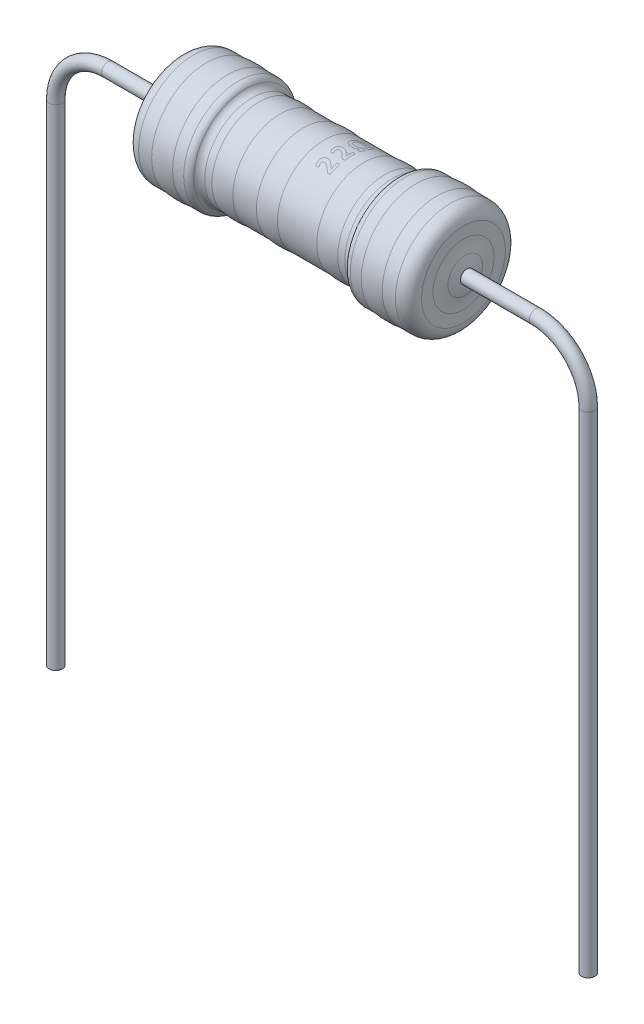
SolidWorks part; units mm, degrees
ref_plane "Front Plane" through (0, 0, 0) normal (0, 0, 1) x (1, 0, 0)
ref_plane "Top Plane" through (0, 0, 0) normal (0, 1, 0) x (1, 0, 0)
ref_plane "Right Plane" through (0, 0, 0) normal (1, 0, 0) x (0, 0, -1)
sketch "Sketch Set Wire Width" plane through (0, 0, 0) normal (0, 0, 1) x (1, 0, 0)
  line L0 (-8.16, 0) -> (8.16, 0)
  line L1 (-10.16, -2) -> (-10.16, -20.6984)
  line L2 (10.16, -2) -> (10.16, -20.6984)
  line L3 (-10.16, -20.6984) -> (10.16, -20.6984) construction
  line L4 (0, 0) -> (0, -20.6984) construction
  arc A0 (-8.16, 0) -> (-10.16, -2) centre (-8.16, -2) ccw
  arc A1 (8.16, 0) -> (10.16, -2) centre (8.16, -2) cw
  dimension "D2" = 2
  dimension "D3" = 60
  dimension "D1" = 20.32
sketch "Sketch Wire Diameter" plane through (0, 0, 0) normal (1, 0, 0) x (0, 0, -1)
  circle A0 centre (0, 0) radius 0.25
  dimension "D1" = 0.5
sweep "SET WIRE LENGTH" add profiles "Sketch Wire Diameter" path "Sketch Set Wire Width"
sketch "Sketch3" plane through (0, 0, 0) normal (0, 0, 1) x (1, 0, 0)
  line L0 (-5.4, 0) -> (5.4, 0)
  line L1 (0, 0) -> (0, 1.8) construction
  line L2 (-2.9, 1.8) -> (2.9, 1.8)
  line L3 (-5.4, 0) -> (-5.4, 1.6)
  line L4 (-4.9, 2.1) -> (-3.18, 2.1)
  line L5 (-2.9, 1.82) -> (-2.9, 1.8)
  line L6 (5.4, 0) -> (5.4, 1.6)
  line L7 (4.9, 2.1) -> (3.18, 2.1)
  line L8 (2.9, 1.82) -> (2.9, 1.8)
  arc A0 (-5.4, 1.6) -> (-4.9, 2.1) centre (-4.9, 1.6) cw
  arc A1 (5.4, 1.6) -> (4.9, 2.1) centre (4.9, 1.6) ccw
  arc A2 (-3.18, 2.1) -> (-2.9, 1.82) centre (-3.18, 1.82) cw
  arc A3 (3.18, 2.1) -> (2.9, 1.82) centre (3.18, 1.82) ccw
  dimension "D5" = 0.5
  dimension "D6" = 0.28
  dimension "D1" = 10.8
  dimension "D2" = 5.8
  dimension "D3" = 1.8
  dimension "D4" = 2.1
revolve "Revolve2" add sketch "Sketch3" angle 360 about L0
fillet "Fillet1" radius 0.3 2 edges at (2.9, 0, 1.8) (-2.9, 0, 1.8)
sketch "Sketch5" plane through (0, 0, 0) normal (0, 0, 1) x (1, 0, 0)
  line L0 (0, 0) -> (2, 0) construction
  line L1 (0, 0) -> (-0.3, 0) construction
  line L2 (-0.3, 0) -> (-2, 0) construction
  line L3 (-2, 0) -> (-4, 0) construction
  line L4 (2, 0) -> (4, 0) construction
  line L5 (-4, 0) -> (-4, 2.1) construction
  line L6 (-0.3, 0) -> (-0.3, 1.8) construction
  line L7 (-2, 0) -> (-2, 1.8) construction
  line L8 (2, 0) -> (2, 1.8) construction
  line L9 (4, 0) -> (4, 2.1) construction
  line L10 (-4, 2.1) -> (-4, 2.13) construction
  line L11 (-4.9, 2.1) -> (-3.18, 2.1) construction
  line L12 (4.9, 2.1) -> (3.18, 2.1) construction
  line L13 (-2.9, 1.8) -> (2.9, 1.8) construction
  line L14 (-2, 1.8) -> (-2, 1.83) construction
  line L17 (-4.4, 2.1) -> (-3.6, 2.1)
  line L19 (-5.4, 0) -> (5.4, 0) construction
  line L22 (-2.4, 1.8) -> (-1.6, 1.8) construction
  line L26 (-0.7, 1.8) -> (0.1, 1.8) construction
  line L30 (1.6, 1.8) -> (2.4, 1.8) construction
  line L34 (3.6, 2.1) -> (4.4, 2.1) construction
  line L36 (-0.3, 1.8) -> (-0.3, 1.83) construction
  line L37 (2, 1.8) -> (2, 1.83) construction
  line L38 (4, 2.1) -> (4, 2.13) construction
  arc A0 (-4.4, 2.1) -> (-3.6, 2.1) centre (-4, -0.5517) cw
  arc A1 (-2.4, 1.8) -> (-1.6, 1.8) centre (-2, -0.8517) cw construction
  arc A2 (-0.7, 1.8) -> (0.1, 1.8) centre (-0.3, -0.8517) cw construction
  arc A3 (1.6, 1.8) -> (2.4, 1.8) centre (2, -0.8517) cw construction
  arc A4 (3.6, 2.1) -> (4.4, 2.1) centre (4, -0.5517) cw construction
  dimension "D3" = 0.8
  dimension "D1" = 4
  dimension "D2" = 4
  dimension "D4" = 0.03
  dimension "D5" = 2
  dimension "D6" = 2
  dimension "D7" = 1.7
revolve "Band 1" add sketch "Sketch5" angle 360 about L2
sketch "Sketch8" plane through (0, 0, 0) normal (0, 0, 1) x (1, 0, 0)
  line L0 (-2.4, 1.8) -> (-1.6, 1.8) construction
  line L1 (-2.4, 1.8) -> (-1.6, 1.8)
  arc A0 (-1.6, 1.8) -> (-2.4, 1.8) centre (-2, -0.8517) ccw construction
  arc A1 (-1.6, 1.8) -> (-2.4, 1.8) centre (-2, -0.8517) ccw
revolve "Band 2" add sketch "Sketch8" angle 360 about L2
sketch "Sketch9" plane through (0, 0, 0) normal (0, 0, 1) x (1, 0, 0)
  line L0 (-0.7, 1.8) -> (0.1, 1.8) construction
  line L1 (-0.7, 1.8) -> (0.1, 1.8)
  arc A0 (0.1, 1.8) -> (-0.7, 1.8) centre (-0.3, -0.8517) ccw construction
  arc A1 (0.1, 1.8) -> (-0.7, 1.8) centre (-0.3, -0.8517) ccw
revolve "Band 3" add sketch "Sketch9" angle 360 about L2
sketch "Sketch10" plane through (0, 0, 0) normal (0, 0, 1) x (1, 0, 0)
  line L0 (1.6, 1.8) -> (2.4, 1.8) construction
  line L1 (1.6, 1.8) -> (2.4, 1.8)
  arc A0 (2.4, 1.8) -> (1.6, 1.8) centre (2, -0.8517) ccw construction
  arc A1 (2.4, 1.8) -> (1.6, 1.8) centre (2, -0.8517) ccw
revolve "Band 4" add sketch "Sketch10" angle 360 about L0
sketch "Sketch11" plane through (0, 0, 0) normal (0, 0, 1) x (1, 0, 0)
  line L0 (3.6, 2.1) -> (4.4, 2.1) construction
  line L1 (3.6, 2.1) -> (4.4, 2.1)
  arc A0 (4.4, 2.1) -> (3.6, 2.1) centre (4, -0.5517) ccw construction
  arc A1 (4.4, 2.1) -> (3.6, 2.1) centre (4, -0.5517) ccw
revolve "Band 5" add sketch "Sketch11" angle 360 about L4
sketch "Sketch12" plane through (0, 0, 0) normal (0, 0, 1) x (1, 0, 0)
  line L0 (-5.35, 0) -> (5.35, 0) construction
  line L1 (-5.35, 1) -> (-5.35, 0)
  line L2 (5.35, 1) -> (5.35, 0)
  line L3 (-5.35, 0) -> (-5.55, 0)
  line L4 (5.35, 0) -> (5.55, 0)
  arc A0 (-5.35, 1) -> (-5.55, 0) centre (-2.95, 0) ccw
  arc A1 (5.35, 1) -> (5.55, 0) centre (2.95, 0) cw
  dimension "D3" = 0.2
  dimension "D4" = 2.6
  dimension "D1" = 10.7
  dimension "D2" = 1
revolve "Revolve10" add sketch "Sketch12" angle 360 about L0
fillet "Fillet2" radius 2 2 edges at (5.4, 0, 0.8703) (-5.4, 0, -0.8703)
ref_plane "Plane2" through (0, 3, 0) normal (0, 1, 0) x (1, 0, 0)
sketch "Sketch13" plane through (0, 3, 0) normal (0, 1, 0) x (1, 0, 0)
  line L0 (0, 0) -> (1.15, 0) construction
  line L1 (1.15, 1.75) -> (1.15, -1.75) construction
  text T0 "22Ω" font "Calibri" height 0.6
  dimension "D1" = 3.5
  dimension "D2" = 1.15
wrap "Wrap1" sketch "Sketch13" wrap type scribe source sketch "Sketch13" face at (0.1, 1.8, 0)
